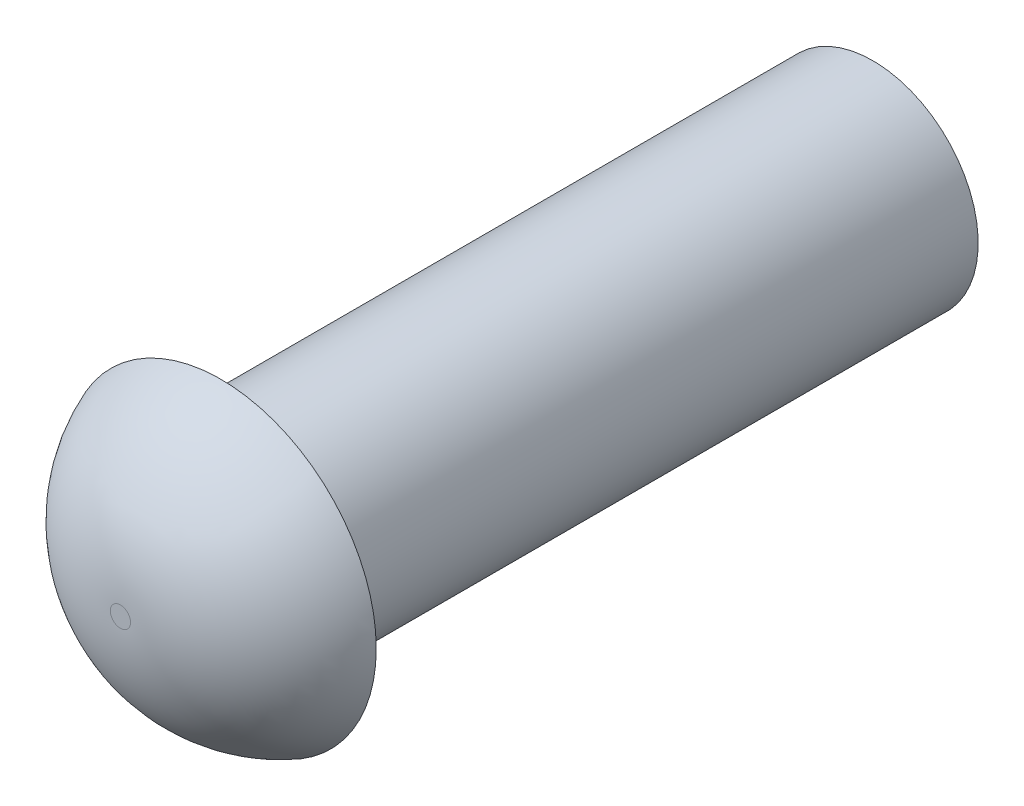
SolidWorks part; units mm, degrees
ref_plane "Płaszczyzna przednia" through (0, 0, 0) normal (0, 0, 1) x (1, 0, 0)
ref_plane "Płaszczyzna górna" through (0, 0, 0) normal (0, 1, 0) x (1, 0, 0)
ref_plane "Płaszczyzna prawa" through (0, 0, 0) normal (1, 0, 0) x (0, 0, -1)
sketch "Szkic1" plane through (0, 0, 0) normal (0, 0, 1) x (1, 0, 0)
  circle A0 centre (0, 0) radius 1.05
  dimension "D1" = 2.1
extrude "Dodanie-wyciągnięcie1" add sketch "Szkic1" along normal blind 6.5
sketch "Szkic2" plane through (0, 0, 6.5) normal (0, 0, 1) x (1, 0, 0)
  circle A0 centre (0, 0) radius 1.55
  dimension "D1" = 3.1
extrude "Dodanie-wyciągnięcie2" add sketch "Szkic2" along normal blind 1
fillet "Zaokrąglenie1" radius 1.55 1 edges at (1.55, 0, 7.5)
